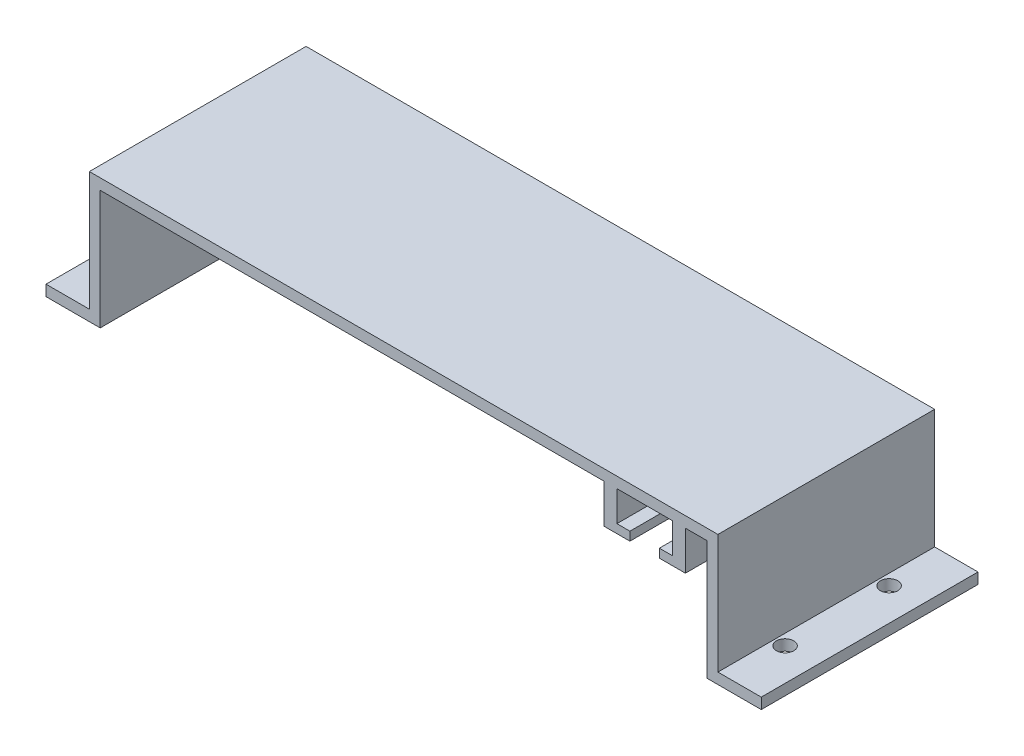
SolidWorks part; units mm, degrees
ref_plane "Front Plane" through (0, 0, 0) normal (0, 0, 1) x (1, 0, 0)
ref_plane "Top Plane" through (0, 0, 0) normal (0, 1, 0) x (1, 0, 0)
ref_plane "Right Plane" through (0, 0, 0) normal (1, 0, 0) x (0, 0, -1)
sketch "Sketch1" plane through (0, 0, 0) normal (0, 1, 0) x (1, 0, 0)
  line L1 (-88.9, 31.75) -> (88.9, 31.75)
  line L2 (-88.9, 31.75) -> (-88.9, -31.75)
  line L3 (-88.9, -31.75) -> (88.9, -31.75)
  line L4 (88.9, 31.75) -> (88.9, -31.75)
  line L5 (-88.9, 31.75) -> (88.9, -31.75) construction
  line L6 (-88.9, -31.75) -> (88.9, 31.75) construction
  point P0 (0, 0)
  dimension "D1" = 177.8
  dimension "D2" = 63.5
extrude "Boss-Extrude1" add sketch "Sketch1" along normal blind 3.175
sketch "Sketch3" plane through (0, 3.175, 0) normal (0, 1, 0) x (1, 0, 0)
  line L0 (-88.9, -31.75) -> (88.9, -31.75) construction
  line L1 (-88.9, 31.75) -> (-92.075, 31.75)
  line L2 (-88.9, 31.75) -> (-88.9, -31.75)
  line L3 (-88.9, -31.75) -> (-92.075, -31.75)
  line L4 (-92.075, 31.75) -> (-92.075, -31.75)
  line L5 (0, -55) -> (0, 55) construction
  line L6 (88.9, -31.75) -> (92.075, -31.75)
  line L7 (92.075, 31.75) -> (92.075, -31.75)
  line L8 (88.9, 31.75) -> (92.075, 31.75)
  line L9 (88.9, 31.75) -> (88.9, -31.75)
  dimension "D1" = 3.175
extrude "Boss-Extrude2" add sketch "Sketch3" against normal blind 38.1
sketch "Sketch4" plane through (92.075, 0, 0) normal (1, 0, 0) x (0, 0, -1)
  line L0 (31.75, -34.925) -> (31.75, 3.175) construction
  line L1 (-31.75, -34.925) -> (31.75, -34.925)
  line L2 (-31.75, -34.925) -> (-31.75, -31.75)
  line L3 (-31.75, -31.75) -> (31.75, -31.75)
  line L4 (31.75, -34.925) -> (31.75, -31.75)
  dimension "D1" = 3.175
extrude "Boss-Extrude3" add sketch "Sketch4" along normal blind 12.7
sketch "Sketch5" plane through (0, -34.925, 0) normal (0, -1, 0) x (1, 0, 0)
  line L0 (88.9, -31.75) -> (88.9, 31.75) construction
  line L1 (104.775, -31.75) -> (88.9, -31.75) construction
  circle A0 centre (95.25, -15.24) radius 2.54
  dimension "D1" = 5.08
  dimension "D2" = 6.35
  dimension "D3" = 16.51
extrude "Cut-Extrude1" cut sketch "Sketch5" against normal blind 12.7
mirror "Mirror1" about plane through (0, 0, 0) normal (1, 0, 0) of "Boss-Extrude3", "Cut-Extrude1"
sketch "Sketch6" plane through (0, 0, 31.75) normal (0, 0, 1) x (1, 0, 0)
  line L0 (58.674, 0) -> (58.674, -11.43)
  line L1 (-88.9, 0) -> (88.9, 0) construction
  line L2 (58.674, -11.43) -> (66.294, -11.43)
  line L3 (66.294, -11.43) -> (66.294, -8.89)
  line L4 (66.294, -8.89) -> (62.484, -8.89)
  line L5 (62.484, -8.89) -> (62.484, 0)
  line L6 (82.55, 0) -> (82.55, -11.43)
  line L7 (82.55, -11.43) -> (74.93, -11.43)
  line L8 (74.93, -11.43) -> (74.93, -8.89)
  line L9 (74.93, -8.89) -> (78.74, -8.89)
  line L10 (78.74, -8.89) -> (78.74, 0)
  line L11 (-88.9, -34.925) -> (-88.9, 0) construction
  line L12 (82.55, 0) -> (78.74, 0)
  line L13 (62.484, 0) -> (58.674, 0)
  dimension "D1" = 11.43
  dimension "D2" = 2.54
  dimension "D3" = 3.81
  dimension "D4" = 3.81
  dimension "D5" = 167.64
  dimension "D6" = 16.256
extrude "Boss-Extrude4" add sketch "Sketch6" against normal up to surface (63.5 mm away) up to face at (0, -21.6958, -31.75)
sketch "Sketch7" plane through (0, -34.925, 0) normal (0, -1, 0) x (1, 0, 0)
  line L0 (88.9, 31.75) -> (104.775, 31.75) construction
  circle A0 centre (95.25, 15.24) radius 2.54
  dimension "D1" = 5.08
  dimension "D2" = 16.51
extrude "Cut-Extrude2" cut sketch "Sketch7" against normal through all
sketch "Sketch8" plane through (0, -31.75, 0) normal (0, 1, 0) x (1, 0, 0)
  line L0 (-104.775, -31.75) -> (-92.075, -31.75) construction
  line L1 (-104.775, 31.75) -> (-104.775, -31.75) construction
  circle A0 centre (-95.25, -15.24) radius 2.54
  dimension "D1" = 5.08
  dimension "D2" = 16.51
  dimension "D3" = 9.525
extrude "Cut-Extrude3" cut sketch "Sketch8" against normal through all
